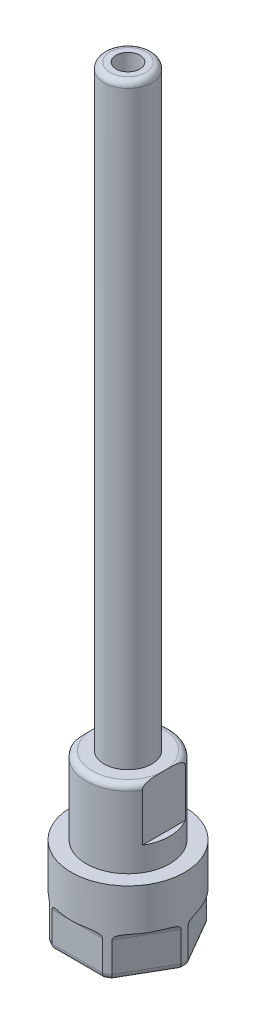
SolidWorks part; units mm, degrees
ref_plane "Front" through (0, 0, 0) normal (0, 0, 1) x (1, 0, 0)
ref_plane "Top" through (0, 0, 0) normal (0, 1, 0) x (1, 0, 0)
ref_plane "Right" through (0, 0, 0) normal (1, 0, 0) x (0, 0, -1)
sketch "Esquisse1" plane through (0, 0, 0) normal (0, 0, 1) x (1, 0, 0)
  line L0 (0, 0) -> (0, 127) construction
  line L1 (4, 127) -> (4, 27)
  line L2 (4, 27) -> (7, 27)
  line L3 (7, 27) -> (7, 14)
  line L4 (7, 14) -> (9.5, 14)
  line L5 (9.5, 14) -> (9.5, 0)
  line L6 (9.5, 0) -> (0, 0)
  line L7 (4, 127) -> (2, 127)
  line L8 (2, 127) -> (2, 123)
  line L9 (2, 123) -> (0, 121)
  line L10 (0, 0) -> (0, 121)
  dimension "D1" = 8
  dimension "D2" = 19
  dimension "D3" = 14
  dimension "D4" = 14
  dimension "D5" = 13
  dimension "D6" = 100
  dimension "D7" = 4
  dimension "D8" = 4
  dimension "D9" = 45
revolve "Révolution1" add sketch "Esquisse1" angle 360 about L0
sketch "Esquisse2" plane through (0, 0, 0) normal (0, -1, 0) x (1, 0, 0)
  circle A0 centre (0, 0) radius 4
  dimension "D1" = 8
extrude "Enlèv. mat.-Extru.1" cut sketch "Esquisse2" against normal blind 8
sketch "Esquisse3" plane through (0, 27, 0) normal (0, 1, 0) x (1, 0, 0)
  line L0 (0, 0) -> (0, 3.3999) construction
  line L1 (6, -3.6056) -> (6, 3.6056)
  line L2 (-6, -3.6056) -> (-6, 3.6056)
  arc A0 (6, 3.6056) -> (6, -3.6056) centre (0, 0) cw
  circle A1 centre (0, 0) radius 7 construction
  arc A2 (-6, 3.6056) -> (-6, -3.6056) centre (0, 0) ccw
  dimension "D1" = 12
extrude "Enlèv. mat.-Extru.2" cut sketch "Esquisse3" against normal blind 9
sketch "Esquisse4" plane through (0, 0, 0) normal (0, -1, 0) x (1, 0, 0)
  line L1 (9.815, 0) -> (4.9075, 8.5)
  line L2 (4.9075, 8.5) -> (-4.9075, 8.5)
  line L3 (-4.9075, 8.5) -> (-9.815, 0)
  line L4 (-9.815, 0) -> (-4.9075, -8.5)
  line L5 (-4.9075, -8.5) -> (4.9075, -8.5)
  line L6 (4.9075, -8.5) -> (9.815, 0)
  circle A0 centre (0, 0) radius 8.5 construction
  circle A1 centre (0, 0) radius 15
  dimension "D2" = 30
  dimension "D1" = 17
extrude "Enlèv. mat.-Extru.3" cut sketch "Esquisse4" against normal blind 7
fillet "Congé1" radius 1 22 edges at (0, 127, -4) (0, 27, 7) (0, 27, -7) (0, 0, -8.5) (-4.75, 0, -8.2272) (-7.3612, 0, -4.25) (-9.5, 0, 0) (-7.3612, 0, 4.25) (-4.75, 0, 8.2272) (0, 0, 8.5) (4.75, 0, 8.2272) (7.3612, 0, 4.25) (9.5, 0, 0) (7.3612, 0, -4.25) (4.75, 0, -8.2272) (0, 0, -4) (0, 7, 8.5) (7.3612, 7, 4.25) (7.3612, 7, -4.25) (0, 7, -8.5) (-7.3612, 7, -4.25) (-7.3612, 7, 4.25)
